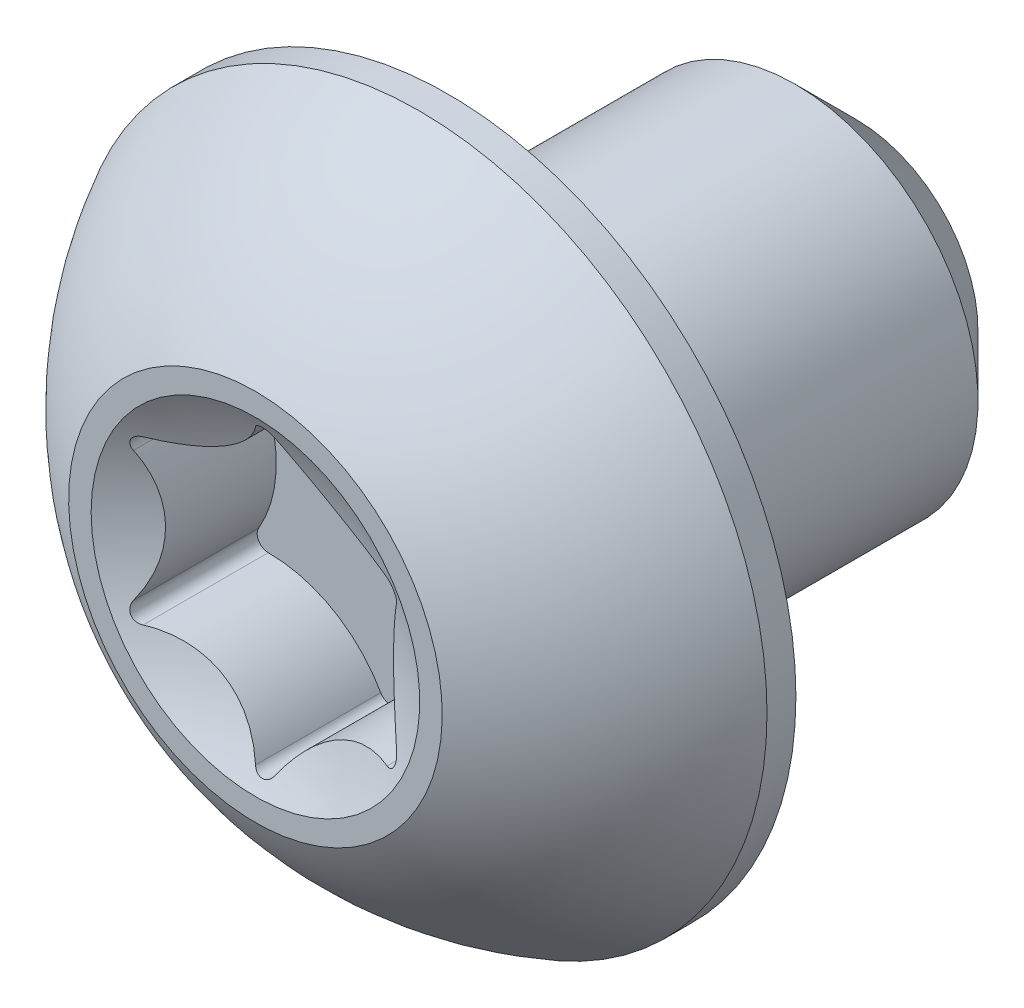
SolidWorks part; units mm, degrees
ref_plane "Front" through (0, 0, 0) normal (0, 0, 1) x (1, 0, 0)
ref_plane "Top" through (0, 0, 0) normal (0, 1, 0) x (1, 0, 0)
ref_plane "Right" through (0, 0, 0) normal (1, 0, 0) x (0, 0, -1)
sketch "Sketch1" plane through (0, 0, 0) normal (1, 0, 0) x (0, 0, -1)
  line L0 (0, 0) -> (4.6736, 0) construction
  line L1 (0, 2.7051) -> (0, 0) construction
  line L2 (1.4986, 0) -> (1.4986, 2.7051) construction
  line L3 (4.6736, 0) -> (4.6736, 1.4224) construction
  line L8 (4.6538, 1.4568) -> (4.9117, 1.01)
  line L9 (4.9911, 1.01) -> (5.2491, 1.4568)
  line L10 (4.6736, 1.4224) -> (1.4986, 1.4224) construction
  line L11 (1.4986, 2.7051) -> (1.2738, 2.7051) construction
  line L12 (4.6736, 0) -> (4.6736, -1.4224) construction
  line L13 (4.6339, 1.4911) -> (5.2689, 1.4911) construction
  line L14 (5.2689, 1.4911) -> (4.9514, 0.9412) construction
  line L15 (4.9514, 0.9412) -> (4.6339, 1.4911) construction
  line L16 (4.9514, 0.9412) -> (4.9514, 1.01) construction
  line L17 (4.9514, 1.4911) -> (4.9514, 1.4224) construction
  line L18 (4.6736, 1.4224) -> (5.2292, 1.4224) construction
  line L19 (4.6538, 1.4568) -> (5.2491, 1.4568)
  line L20 (4.9117, 1.01) -> (4.9911, 1.01)
  arc A0 (0, 1.4526) -> (1.2738, 2.7051) centre (2.6809, 0) cw construction
  point P8 (0, 1.1821)
  point P19 (1.049, 0)
  point P21 (0, 0.8866)
  point P26 (3.0861, -1.4224)
  point P37 (4.9514, 1.4224)
  point P39 (4.9514, 1.4568)
  point P42 (4.9514, 1.01)
  dimension "Thread Pitch" = 0.635
sketch "Sketch2" plane through (0, 0, 0) normal (1, 0, 0) x (0, 0, -1)
  line L0 (1.4986, 2.7051) -> (1.4986, 1.4224) construction
  line L1 (1.4986, 0) -> (1.4986, 2.7051) construction
  line L2 (4.6736, 1.4224) -> (1.4986, 1.4224) construction
  line L3 (1.4986, 1.4224) -> (4.1973, 1.4224)
  line L4 (4.6736, 0.9462) -> (4.6736, 0)
  line L5 (4.6736, 0) -> (1.4986, 0)
  line L6 (0, 0) -> (0, 1.4526) construction
  line L7 (1.2738, 2.7051) -> (1.4986, 2.7051) construction
  line L8 (4.1973, 1.4224) -> (4.6736, 0.9462)
  line L9 (1.4986, 1.4224) -> (1.4986, 0)
  arc A0 (1.2738, 2.7051) -> (0, 1.4526) centre (2.6809, 0) ccw construction
  arc A1 (1.2738, 2.7051) -> (0, 1.4526) centre (2.6809, 0) ccw construction
  point P11 (4.6736, 1.4224)
  dimension "D1" = 0.4763
  dimension "D2" = 45
revolve "Revolve1" add sketch "Sketch2" angle 360 about L5
sketch "Sketch3" plane through (0, 0, 0) normal (1, 0, 0) x (0, 0, -1)
  line L0 (1.4986, 0) -> (1.4986, 2.7051) construction
  line L1 (1.4986, 2.7051) -> (1.2738, 2.7051) construction
  line L2 (1.4986, 0) -> (1.4986, 2.7051)
  line L3 (1.4986, 2.7051) -> (1.2738, 2.7051)
  line L4 (0, 1.4526) -> (0, 0)
  line L5 (0, 0) -> (1.4986, 0)
  arc A0 (1.2738, 2.7051) -> (0, 1.4526) centre (2.6809, 0) ccw construction
  arc A1 (1.2738, 2.7051) -> (0, 1.4526) centre (2.6809, 0) ccw
revolve "Revolve2" add sketch "Sketch3" angle 360 about L5
combine bodies "Combine1" operation type add bodies to combine 114 109
sketch "Sketch4" plane through (0, 0, 0) normal (0, 0, 1) x (1, 0, 0)
  line L0 (-0.8866, 0) -> (0, 0)
  line L2 (0, 0) -> (-1.0238, 0.5911)
  line L3 (0, 0) -> (-2.7051, 0) construction
  line L6 (0, 0.1774) -> (-1.0238, 0.5911) construction
  circle A0 centre (0, 0) radius 1.1821 construction
  circle A1 centre (0, 0) radius 0.8866 construction
  circle A2 centre (0, 0) radius 2.7051 construction
  arc A4 (-0.8866, 0) -> (-1.0235, 0.5051) centre (-1.8867, 0) ccw
  arc A5 (-1.0238, 0.5911) -> (-1.0235, 0.5051) centre (-0.9496, 0.5483) ccw
  circle A7 centre (0, 0) radius 0.1774 construction
  point P4 (-1.1821, 0)
  point P5 (-0.8866, 0)
  point P12 (0, -0.8866)
  dimension "D4" = 1.0001
  dimension "D3" = 30
  dimension "D5" = 8
extrude "Cut-Extrude1" cut sketch "Sketch4" against normal blind 1.049
mirror "Mirror1" about plane through (0, 0, 0) normal (0, 1, 0) of "Cut-Extrude1"
pattern_circular "CirPattern1" count 6 over 360 about axis through (0, 0, -4.6736) along (0, 0, -1) of "Cut-Extrude1", "Mirror1"
sketch "Sketch5" plane through (0, 0, 0) normal (1, 0, 0) x (0, 0, -1)
  line L0 (0, 0) -> (0.3497, 0) construction
  line L1 (-2.1599, 2.5096) -> (-2.1599, -2.5096)
  line L2 (0, 0) -> (0.1748, 0) construction
  line L3 (0, 1.4526) -> (0, -1.4526) construction
  line L4 (0, 1.4526) -> (0, 1.2778) construction
  arc A0 (-2.1599, -2.5096) -> (-2.1599, 2.5096) centre (-2.1599, 0) ccw
  dimension "D1" = 0.3497
revolve "Cut-Revolve1" cut sketch "Sketch5" angle 360 about L1
split "Split1" [suppressed] bodies to split 113
sketch "Sketch6" [suppressed] plane through (0, 0, -4.6736) normal (0, 0, -1) x (-1, 0, 0)
  circle A0 centre (0, 0) radius 1.4224
curve "Helix/Spiral1" [suppressed] pitch 0.635 height 3.81 turns 6
sketch "Sketch7" [suppressed] plane through (0, 0, 0) normal (1, 0, 0) x (0, 0, -1)
  line L0 (4.6538, 1.4568) -> (5.2491, 1.4568)
  line L1 (5.2491, 1.4568) -> (4.9911, 1.01)
  line L2 (4.9911, 1.01) -> (4.9117, 1.01)
  line L3 (4.9117, 1.01) -> (4.6538, 1.4568)
sweep "Cut-Sweep1" [suppressed] cut profiles "Sketch7" path "Helix/Spiral1"
sketch "Sketch8" [suppressed] plane through (0, 0, -1.4986) normal (0, 0, -1) x (-1, 0, 0)
  circle A0 centre (0, 0) radius 1.4224 construction
  circle A2 centre (0, 0) radius 1.4732
  dimension "D1" = 0.0508
extrude "Boss-Extrude1" [suppressed] add sketch "Sketch8" along normal up to next draft 20
equation "\"Approx Screw Head Flat@Sketch1\" = \"Head Height@Sketch1\" * .15"
equation "\"Approx Drive Depth@Sketch1\" = \"Head Height@Sketch1\" * .7"
equation "\"D1@Cut-Extrude1\" = \"Approx Drive Depth@Sketch1\""
equation "\"D1@Sketch5\" = \"Approx Drive Depth@Sketch1\" / 3"
equation "\"D1@Sketch2\" = \"Thread Pitch@Sketch1\" * .75"
equation "\"Approx Drive Gap@Sketch1\" = \"Head Diameter@Sketch1\" * .05"
equation "\"Approx Min Drive Size@Sketch1\" = \"Approx Drive Size @Sketch1\" * .75"
equation "\"Thread Note@Sketch1\" = \"Thread Pitch@Sketch1\" * 2.5"
equation "\"Pitch/8@Sketch1\" = \"Thread Pitch@Sketch1\" / 8"
equation "\"D4@Helix/Spiral1\" = \"Thread Pitch@Sketch1\""
equation "\"D3@Helix/Spiral1\" = \"Length@Sketch1\" + \"Thread Pitch@Sketch1\""
equation "\"Approx Drive Size @Sketch1\"  = \"Head Diameter@Sketch1\"*.437"
equation "\"D4@Sketch4\"=\"Approx Min Drive Size@Sketch1\"*.564"
